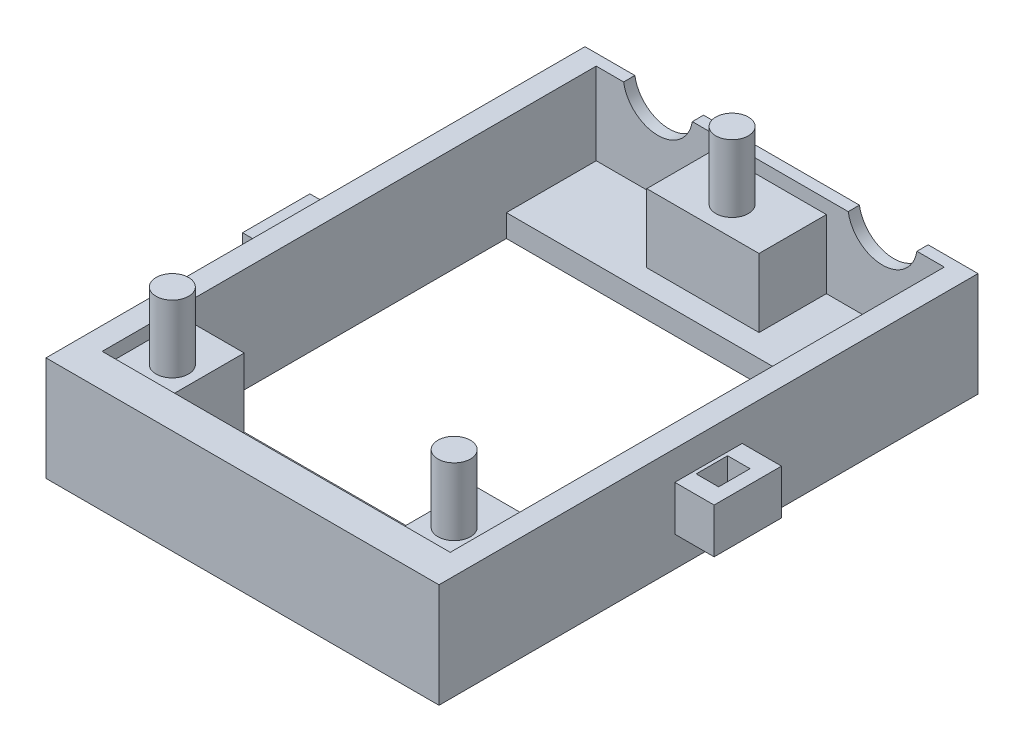
SolidWorks part; units mm, degrees
ref_plane "Front Plane" through (0, 0, 0) normal (0, 0, 1) x (1, 0, 0)
ref_plane "Top Plane" through (0, 0, 0) normal (0, 1, 0) x (1, 0, 0)
ref_plane "Right Plane" through (0, 0, 0) normal (1, 0, 0) x (0, 0, -1)
sketch "Sketch1" plane through (0, 0, 0) normal (0, 1, 0) x (1, 0, 0)
  line L1 (-17.5, 24) -> (17.5, 24)
  line L2 (-17.5, 24) -> (-17.5, -24)
  line L3 (-17.5, -24) -> (17.5, -24)
  line L4 (17.5, 24) -> (17.5, -24)
  line L5 (-44.2539, 0) -> (44.2539, 0) construction
  line L6 (0, -44.7868) -> (0, 44.7868) construction
  dimension "D2" = 35
  dimension "D1" = 48
  dimension "D3" = 24
  dimension "D4" = 17.5
extrude "Boss-Extrude1" add sketch "Sketch1" along normal blind 2
sketch "Sketch2" plane through (0, 2, 0) normal (0, 1, 0) x (1, 0, 0)
  line L1 (-15.5, 23) -> (15.5, 23)
  line L2 (-15.5, 23) -> (-15.5, -21)
  line L3 (-15.5, -21) -> (15.5, -21)
  line L4 (15.5, 23) -> (15.5, -21)
  line L6 (17.5, -24) -> (17.5, 24) construction
  line L7 (-17.5, -24) -> (17.5, -24) construction
  line M5 (-17.5, 24) -> (-17.5, -24)
  line M6 (-17.5, -24) -> (17.5, -24)
  line M7 (17.5, -24) -> (17.5, 24)
  line M8 (17.5, 24) -> (-17.5, 24)
  dimension "D1" = 2
  dimension "D2" = 3
  dimension "D3" = 31
  dimension "D4" = 44
extrude "Boss-Extrude2" add sketch "Sketch2" along normal blind 7.3 contours L1 L4 L3 L2 M8 M5 M6 M7 region at (0, 2, -23.4059)
sketch "Sketch3" plane through (0, 2, 0) normal (0, 1, 0) x (1, 0, 0)
  line L0 (-15.5, 23) -> (15.5, 23) construction
  line L1 (-5, 23) -> (5, 23)
  line L2 (-5, 23) -> (-5, 17)
  line L3 (-5, 17) -> (5, 17)
  line L4 (5, 23) -> (5, 17)
  line L5 (15.5, 23) -> (15.5, -21) construction
  line L7 (-15.5, -21) -> (-10.25, -21)
  line L8 (-15.5, -21) -> (-15.5, -13.6)
  line L9 (-15.5, -13.6) -> (-10.25, -13.6)
  line L10 (-10.25, -21) -> (-10.25, -13.6)
  line L11 (15.5, -21) -> (10.25, -21)
  line L12 (15.5, -21) -> (15.5, -13.6)
  line L13 (15.5, -13.6) -> (10.25, -13.6)
  line L14 (10.25, -21) -> (10.25, -13.6)
  dimension "D1" = 10
  dimension "D2" = 6
  dimension "D3" = 10.5
  dimension "D4" = 5.25
  dimension "D5" = 5.25
  dimension "D6" = 7.4
  dimension "D7" = 7.4
extrude "Boss-Extrude3" add sketch "Sketch3" along normal blind 6.1
sketch "Sketch6" plane through (0, 0, -24) normal (0, 0, -1) x (-1, 0, 0)
  line L1 (-17.5, 9.3) -> (17.5, 9.3) construction
  line L2 (-17.5, 9.3) -> (-17.5, 0) construction
  arc A0 (-6.9406, 9.3) -> (-13.0594, 9.3) centre (-10, 9.8) cw
  arc A1 (13.0594, 9.3) -> (6.9406, 9.3) centre (10, 9.8) cw
  line M3 (17.5, 9.3) -> (-17.5, 9.3)
  dimension "D1" = 7.5
  dimension "D3" = 0.5
  dimension "D4" = 0.5
  dimension "D5" = 3.1
  dimension "D6" = 3.1
  dimension "D2" = 20
sketch "Sketch8" plane through (0, 0, 0) normal (0, 1, 0) x (1, 0, 0)
  line L0 (0, -44.7868) -> (0, 44.7868) construction
  line L1 (-17.5, -24) -> (17.5, -24) construction
  line L2 (17.5, 24) -> (-17.5, 24) construction
  line L4 (-17.5, -24) -> (17.5, -24) construction
  circle A0 centre (-12.55, -17.7) radius 1.45
  circle A1 centre (12.55, -17.7) radius 1.45
  circle A2 centre (0, 19.6) radius 1.45
  dimension "D1" = 2.9
  dimension "D7" = 2.9
  dimension "D8" = 2.9
  dimension "D2" = 6.3
  dimension "D4" = 6.3
  dimension "D3" = 25.1
  dimension "D5" = 12.55
  dimension "D6" = 4.4
sketch "Sketch9" plane through (0, 0, 0) normal (0, 1, 0) x (1, 0, 0)
  line L0 (-35.1135, -20.6) -> (29.9959, -20.6) construction
  line L1 (-15.5, 23) -> (15.5, 23) construction
  line L2 (-35.1135, 21.9) -> (32.5575, 21.9) construction
  point P4 (0, 23)
  dimension "D1" = 43.6
  dimension "D2" = 42.5
extrude "Cut-Extrude5" cut sketch "Sketch6" against normal blind 1 contours A0 M3 | A1 M3 region at (-10, 8.2103, -24) region at (10, 8.2103, -24)
sketch "Sketch10" plane through (0, 2, 0) normal (0, 1, 0) x (1, 0, 0)
  line L0 (-15.5, -13.6) -> (15.5, -13.6)
  line L1 (-15.5, 23) -> (-15.5, -13.6) construction
  line L2 (15.5, 23) -> (15.5, -21) construction
  line L3 (-35.1135, -20.6) -> (29.9959, -20.6) construction
  line L4 (-15.5, 15) -> (15.5, 15)
  line L5 (15.5, 23) -> (15.5, -13.6) construction
  line L6 (-35.1135, 21.9) -> (32.5575, 21.9) construction
  line M5 (15.5, -13.6) -> (15.5, 23)
  line M11 (-15.5, 23) -> (-15.5, -13.6)
  dimension "D1" = 7
  dimension "D2" = 6.9
extrude "Cut-Extrude6" cut sketch "Sketch10" against normal through all contours L4 L0 M11 M5 region at (0, 2, -0.7)
extrude "Boss-Extrude4" add sketch "Sketch8" along normal blind 6 from surface starting at face at (0, 8.1, -20)
sketch "Sketch12" plane through (-17.5, 0, 0) normal (-1, 0, 0) x (0, 0, 1)
  line L0 (0, -44.2539) -> (0, 44.2539) construction
  line L1 (-3, 6.7) -> (3, 6.7)
  line L2 (-3, 6.7) -> (-3, 2.7)
  line L3 (-3, 2.7) -> (3, 2.7)
  line L4 (3, 6.7) -> (3, 2.7)
  line L5 (-24, 9.3) -> (24, 9.3) construction
  dimension "D1" = 6
  dimension "D2" = 4
  dimension "D3" = 3
  dimension "D4" = 2.6
extrude "Boss-Extrude5" add sketch "Sketch12" along normal blind 3.5
sketch "Sketch13" plane through (0, 6.7, 0) normal (0, 1, 0) x (1, 0, 0)
  line L0 (-44.2539, 0) -> (44.2539, 0) construction
  line L1 (-17.8, 1.4) -> (-19.8, 1.4)
  line L2 (-17.8, 1.4) -> (-17.8, -1.4)
  line L3 (-17.8, -1.4) -> (-19.8, -1.4)
  line L4 (-19.8, 1.4) -> (-19.8, -1.4)
  line L6 (-21, -3) -> (-21, 3) construction
  dimension "D1" = 2
  dimension "D2" = 2.8
  dimension "D3" = 1.4
  dimension "D4" = 1.2
extrude "Cut-Extrude7" cut sketch "Sketch13" against normal up to surface (4 mm away) up to face at (-19.25, 2.7, 0)
mirror "Mirror1" about plane through (0, 0, 0) normal (1, 0, 0) of "Boss-Extrude5", "Cut-Extrude7"
equation "\"fWidth\"=35"
equation "\"D2@Sketch1\"=\"fWidth\""
equation "\"fLength\"= 48"
equation "\"D1@Sketch1\"=\"fLength\""
equation "\"D3@Sketch1\"=\"fLength\"/2"
equation "\"D4@Sketch1\"=\"fWidth\"/2"
equation "\"wThickness\"=2"
equation "\"D1@Sketch2\"=\"wThickness\""
equation "\"D3@Sketch2\"=\"fWidth\"- 2* \"wThickness\""
equation "\"D4@Sketch2\"=\"fLength\"- 2 *\"wThickness\""
equation "\"wHeight\" = 7.3"
equation "\"D1@Boss-Extrude2\"=\"wHeight\""
equation "\"D3@Sketch3\"=(\"fWidth\"- 2 *\"wThickness\" - 10)/2"
equation "\"D1@Boss-Extrude3\"=\"wHeight\""
equation "\"holeDiam\"= 2.9"
equation "\"D8@Sketch8\"=\"holeDiam\""
equation "\"D1@Sketch8\"=\"holeDiam\""
equation "\"D7@Sketch8\"=\"holeDiam\""
